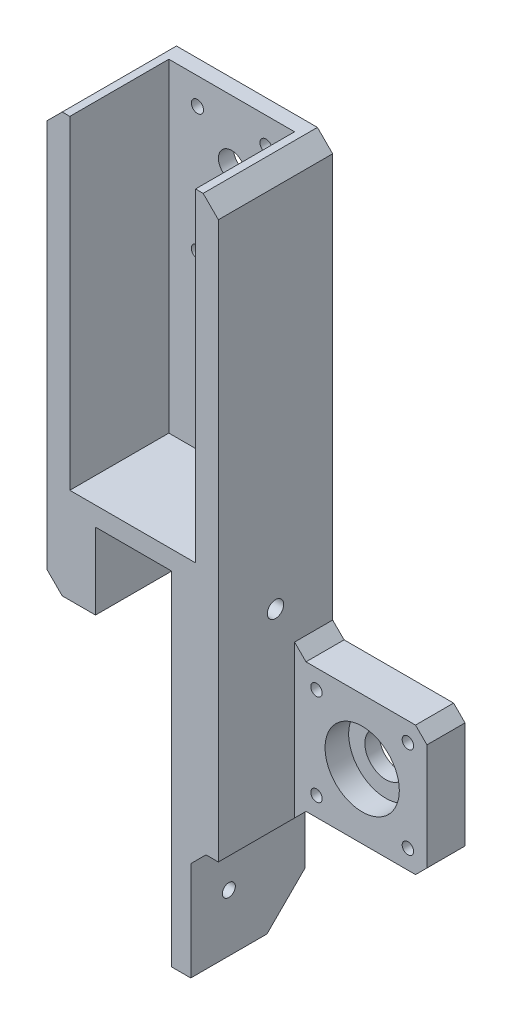
SolidWorks part; units mm, degrees
ref_plane "前视基准面" through (0, 0, 0) normal (0, 0, 1) x (1, 0, 0)
ref_plane "上视基准面" through (0, 0, 0) normal (0, 1, 0) x (1, 0, 0)
ref_plane "右视基准面" through (0, 0, 0) normal (1, 0, 0) x (0, 0, -1)
sketch "草图1" plane through (0, 0, 0) normal (0, 0, 1) x (1, 0, 0)
  line L0 (7.5, 40) -> (25.5, 7) construction
  line L1 (0, 0) -> (33, 0)
  line L2 (0, 0) -> (0, 47)
  line L3 (0, 47) -> (33, 47)
  line L4 (33, 0) -> (33, 47)
  circle A0 centre (7.5, 40) radius 1.6
  circle A1 centre (25.5, 40) radius 1.6
  circle A2 centre (7.5, 7) radius 1.6
  circle A3 centre (25.5, 7) radius 1.6
  circle A4 centre (16.5, 31) radius 3.5
  point P13 (0, 23.5)
  point P14 (16.5, 23.5)
  point P15 (16.5, 47)
  dimension "D5" = 3.2
  dimension "D6" = 7
  dimension "D1" = 18
  dimension "D2" = 33
  dimension "D3" = 33
  dimension "D4" = 47
  dimension "D7" = 9
extrude "凸台-拉伸1" add sketch "草图1" along normal blind 4
sketch "草图3" plane through (0, 0, 0) normal (0, 0, -1) x (-1, 0, 0)
  line L0 (0, -38) -> (-33, -38)
  line L1 (0, 47) -> (6, 47)
  line L2 (0, 47) -> (0, -38)
  line L4 (6, 47) -> (6, -63)
  line L5 (-33, 47) -> (-39, 47)
  line L6 (-33, 47) -> (-33, -38)
  line L8 (-39, 47) -> (-39, -63)
  line L9 (6, -63) -> (-6.25, -63)
  line L10 (-6.25, -63) -> (-6.25, -43)
  line L11 (-6.25, -43) -> (-26.75, -43)
  line L12 (-26.75, -43) -> (-26.75, -63)
  line L13 (-26.75, -63) -> (-39, -63)
  point P2 (-16.5, -38)
  point P14 (-16.5, -43)
  dimension "D1" = 6
  dimension "D2" = 6
  dimension "D3" = 25
  dimension "D4" = 110
  dimension "D5" = 20.5
  dimension "D6" = 20
extrude "凸台-拉伸2" add sketch "草图3" against normal blind 30
sketch "草图4" plane through (0, 0, 0) normal (0, 0, -1) x (-1, 0, 0)
  line L1 (-33, -38) -> (0, -38)
  line L2 (-33, -38) -> (-33, 0)
  line L3 (-33, 0) -> (0, 0)
  line L4 (0, -38) -> (0, 0)
extrude "凸台-拉伸3" add sketch "草图4" against normal up to surface (4 mm away) up to face at (16.5, 23.5, 4)
sketch "草图6" plane through (0, 0, 0) normal (0, 0, -1) x (-1, 0, 0)
  line L0 (-26.75, -63) -> (-26.75, -103)
  line L2 (-26.75, -103) -> (-76.75, -103)
  line L3 (-76.75, -103) -> (-76.75, -63)
  line L4 (-76.75, -63) -> (-26.75, -63)
  line L5 (-26.75, -63) -> (-26.75, -43) construction
  circle A0 centre (-56.75, -83) radius 5.5
  circle A1 centre (-68.75, -95) radius 1.5
  circle A2 centre (-68.75, -71) radius 1.5
  circle A3 centre (-44.75, -95) radius 1.5
  circle A4 centre (-44.75, -71) radius 1.5
  dimension "D3" = 11
  dimension "D10" = 3
  dimension "D1" = 40
  dimension "D2" = 50
  dimension "D4" = 20
  dimension "D5" = 20
  dimension "D6" = 12
  dimension "D7" = 12
  dimension "D8" = 12
  dimension "D9" = 12
extrude "凸台-拉伸4" add sketch "草图6" against normal through all
sketch "草图7" plane through (0, 0, 30) normal (0, 0, 1) x (1, 0, 0)
  line L1 (76.75, -103) -> (39, -103)
  line L2 (76.75, -103) -> (76.75, -63)
  line L3 (76.75, -63) -> (39, -63)
  line L4 (39, -103) -> (39, -63)
extrude "切除-拉伸1" cut sketch "草图7" against normal blind 20 contours L1 L4 L3 L2
sketch "草图8" plane through (0, 0, 10) normal (0, 0, 1) x (1, 0, 0)
  circle A0 centre (56.75, -83) radius 9.75
  dimension "D1" = 19.5
extrude "切除-拉伸2" cut sketch "草图8" against normal blind 6.2
sketch "草图10" plane through (-6, 0, 0) normal (-1, 0, 0) x (0, 0, 1)
  line L0 (30, -63) -> (0, -63) construction
  circle A0 centre (15, -53) radius 2.15
  point P4 (15, -63)
  dimension "D2" = 4.3
  dimension "D1" = 10
extrude "切除-拉伸4" cut sketch "草图10" against normal through all contours A0
sketch "草图11" plane through (26.75, 0, 0) normal (-1, 0, 0) x (0, 0, 1)
  line L1 (30, -103) -> (0, -103)
  line L2 (30, -103) -> (30, -133)
  line L3 (30, -133) -> (0, -133)
  line L4 (0, -103) -> (0, -133)
  circle A3 centre (20, -118) radius 1.7
  dimension "D5" = 20
  dimension "D1" = 15
  dimension "D3" = 3.4
  dimension "D2" = 30
extrude "凸台-拉伸5" add sketch "草图11" against normal blind 5
sketch "草图12" plane through (0, 0, 10) normal (0, 0, 1) x (1, 0, 0)
  line L0 (39, -103) -> (76.75, -103)
  line L5 (76.75, -103) -> (76.75, -63)
  line L6 (76.75, -63) -> (39, -63)
  line L7 (39, -63) -> (39, -66)
  line L8 (39, 47) -> (39, -103) construction
  line L9 (39, -66) -> (73.75, -66)
  line L10 (73.75, -66) -> (73.75, -100)
  line L11 (73.75, -100) -> (39, -100)
  line L12 (39, -100) -> (39, -103)
  dimension "D1" = 3
  dimension "D2" = 3
  dimension "D3" = 3
extrude "切除-拉伸5" cut sketch "草图12" against normal blind 20
chamfer "倒角1" distance 4 angle 45 4 edges at (-6, -63, 15) (-6, 47, 15) (39, 47, 15) (31.75, -103, 15)
chamfer "倒角2" distance 3 angle 45 4 edges at (39, -66, 5) (73.75, -66, 5) (73.75, -100, 5) (39, -100, 5)
chamfer "倒角3" distance 10 angle 45 1 edges at (29.25, -133, 0)
sketch "草图13" plane through (6.25, 0, 0) normal (1, 0, 0) x (0, 0, -1)
  line L4 (0, -63) -> (0, -43)
  line L5 (0, -43) -> (-30, -43)
  line L6 (-30, -43) -> (-30, -63)
  line L7 (-30, -63) -> (0, -63)
  line L8 (0, -63) -> (0, -43)
  line L9 (0, -43) -> (-30, -43)
  line L10 (-30, -43) -> (-30, -63)
  line L11 (-30, -63) -> (0, -63)
  circle A0 centre (-15, -53) radius 2.15 construction
  circle A1 centre (-15, -53) radius 2.15
  dimension "D1" = 0
extrude "凸台-拉伸6" add sketch "草图13" along normal blind 0.5
